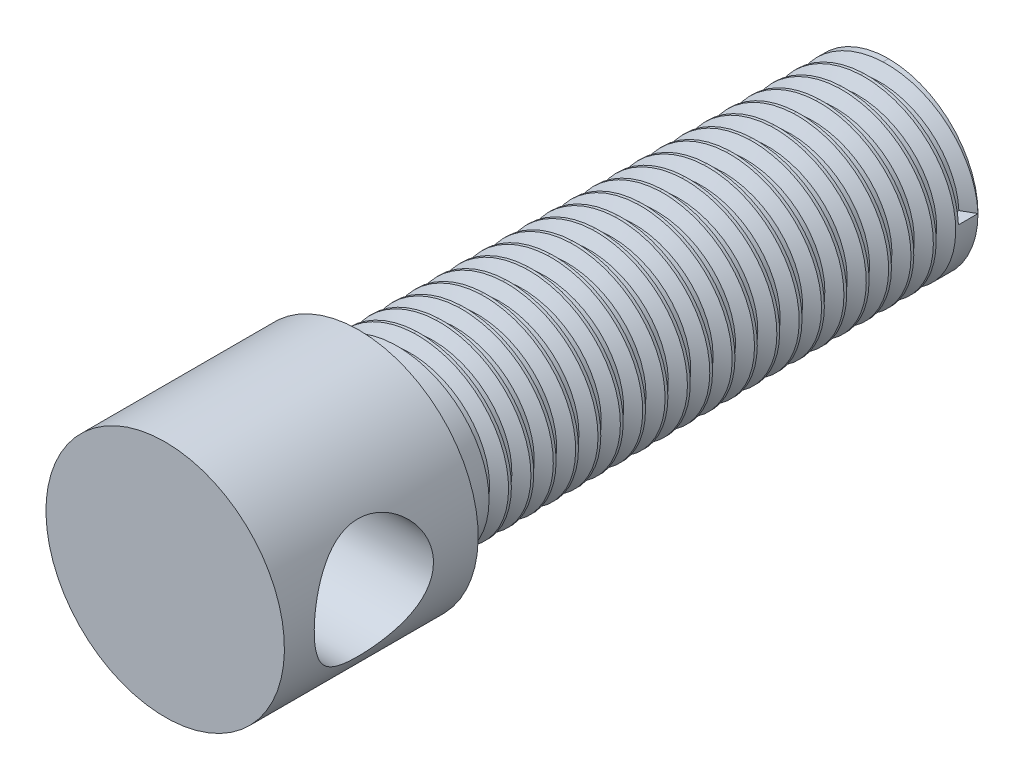
SolidWorks part; units mm, degrees
ref_plane "Спереди" through (0, 0, 0) normal (0, 0, 1) x (1, 0, 0)
ref_plane "Сверху" through (0, 0, 0) normal (0, 1, 0) x (1, 0, 0)
ref_plane "Справа" through (0, 0, 0) normal (1, 0, 0) x (0, 0, -1)
sketch "Эскиз5" plane through (0, 0, 0) normal (1, 0, 0) x (0, 0, -1)
  line L0 (0, 0) -> (-3.4641, 6)
  line L1 (-3.4641, 6) -> (-38.5, 6)
  line L2 (0, 0) -> (-52, 0)
  line L3 (-52, 0) -> (-52, 8)
  line L4 (-52, 8) -> (-39, 8)
  line L5 (-39, 8) -> (-39, 6.5)
  arc A0 (-38.5, 6) -> (-39, 6.5) centre (-38.5, 6.5) cw
  dimension "D6" = 0.5
  dimension "D1" = 60
  dimension "D2" = 52
  dimension "D3" = 6
  dimension "D4" = 8
  dimension "D5" = 13
revolve "Повернуть1" add sketch "Эскиз5" angle 360 about L2 region at (0, 3.2862, 28.3374)
sketch "Эскиз6" plane through (0, 0, 0) normal (1, 0, 0) x (0, 0, -1)
  line L0 (-52, 8) -> (-52, -8) construction
  circle A0 centre (-46, 0) radius 4
  dimension "D1" = 8
  dimension "D2" = 6
extrude "Вырез-Вытянуть3" cut sketch "Эскиз6" against normal through all both and the other way through all
thread "Резьба2" pitch 1.5 method cut trim with start face yes profile "Профиль резьбы3" start angle 0, offset 0, length 32.54, pitch 1.5, diameter 12
ref_plane "Плоскость3" through (6, 0, 3.4641) normal (0, -1, 0) x (1, 0, 0)
sketch "Профиль резьбы3" plane through (6, 0, 3.4641) normal (0, -1, 0) x (1, 0, 0)
  line L0 (0, 0) -> (0, 1.5) construction
  line L11 (0, 0) -> (0, 1.3125)
  line L12 (0, 1.3125) -> (-0.8119, 0.8437)
  line L13 (-0.8119, 0.8437) -> (-0.8119, 0.4687)
  line L15 (-0.8119, 0.4687) -> (0, 0)
  line L17 (-0.8119, 0.6562) -> (0, 0.6562) construction
  point P2 (0, 0)
  dimension "Pitch" = 1.5
  dimension "Profile_Angle" = 60
  dimension "Profile_Land" = 0.375
  dimension "Profile_Height" = 0.8119
